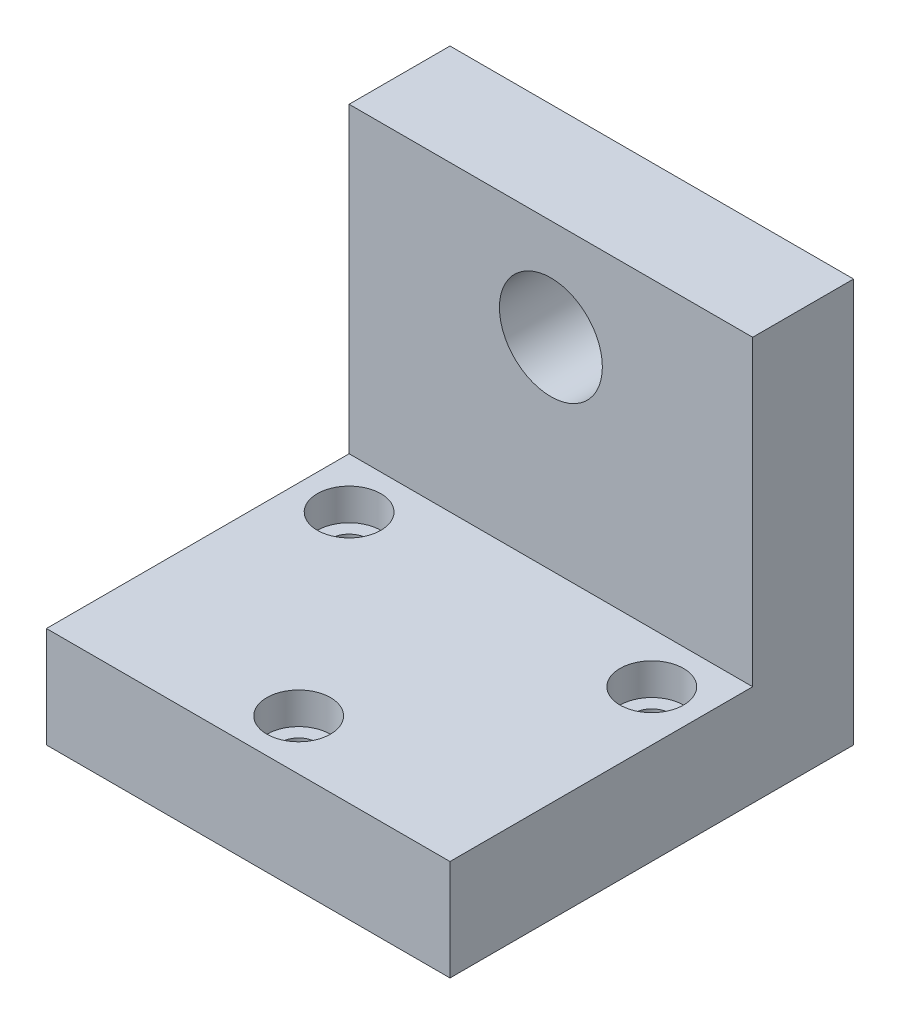
SolidWorks part; units mm, degrees
ref_plane "Front Plane" through (0, 0, 0) normal (0, 0, 1) x (1, 0, 0)
ref_plane "Top Plane" through (0, 0, 0) normal (0, 1, 0) x (1, 0, 0)
ref_plane "Right Plane" through (0, 0, 0) normal (1, 0, 0) x (0, 0, -1)
sketch "Sketch1" plane through (0, 0, 0) normal (0, 0, 1) x (1, 0, 0)
  line L1 (0, 0) -> (25.4, 0)
  line L2 (0, 0) -> (0, 25.4)
  line L3 (0, 25.4) -> (25.4, 25.4)
  line L4 (25.4, 0) -> (25.4, 25.4)
  dimension "D1" = 25.4
  dimension "D2" = 25.4
extrude "Boss-Extrude1" add sketch "Sketch1" along normal mid plane 6.35 from offset 0
sketch "Sketch2" plane through (0, 0, 3.175) normal (0, 0, 1) x (1, 0, 0)
  line L0 (0, 25.4) -> (0, 0) construction
  line L1 (0, 6.35) -> (25.4, 6.35)
  line L2 (0, 6.35) -> (0, 0)
  line L3 (0, 0) -> (25.4, 0)
  line L4 (25.4, 6.35) -> (25.4, 0)
  dimension "D1" = 6.35
extrude "Boss-Extrude2" add sketch "Sketch2" along normal blind 19.05
sketch "Sketch4" plane through (0, 6.35, 0) normal (0, 1, 0) x (1, 0, 0)
  line L0 (0, -22.225) -> (0, -3.175) construction
  line L1 (25.4, -3.175) -> (0, -3.175) construction
  line L2 (25.4, -22.225) -> (25.4, -3.175) construction
  line L3 (25.4, -22.225) -> (0, -22.225) construction
  circle A0 centre (3.175, -6.35) radius 1.127
  circle A1 centre (22.225, -6.35) radius 1.127
  circle A2 centre (12.7, -19.05) radius 1.127
  point P10 (0, 0)
  point P13 (0, 0)
  point P16 (12.7, -22.225)
  dimension "D1" = 2.254
  dimension "D2" = 3.175
  dimension "D3" = 3.175
  dimension "D4" = 3.175
  dimension "D5" = 3.175
extrude "Cut-Extrude2" cut sketch "Sketch4" against normal through all
sketch "Sketch9" plane through (0, 6.35, 0) normal (0, 1, 0) x (1, 0, 0)
  circle A0 centre (3.175, -6.35) radius 2
  circle A1 centre (22.225, -6.35) radius 2
  circle A2 centre (12.7, -19.05) radius 2
  dimension "D1" = 4
extrude "Cut-Extrude4" cut sketch "Sketch9" against normal blind 2
sketch "Sketch3" plane through (0, 0, 3.175) normal (0, 0, 1) x (1, 0, 0)
  line L6 (25.4, 25.4) -> (0, 25.4) construction
  circle A0 centre (12.7, 19.05) radius 3.2385
  point P2 (0, 0)
  point P3 (0, 0)
  point P4 (0, 0)
  point P8 (12.7, 25.4)
  dimension "D2" = 6.477
  dimension "D1" = 19.05
extrude "Cut-Extrude1" cut sketch "Sketch3" against normal through all both and the other way through all
equation "\"tightTol\"= 0.005in"
equation "\"normTol\"= 0.01in"
equation "\"looseTol\"= 0.02in"
equation "\"D2@Sketch3\"=0.25+\"tightTol\""
equation "\"D1@Sketch4\"=2mm+\"normTol\""
equation "\"D1@Sketch9\"=4mm"
equation "\"D1@Cut-Extrude4\"=2mm"
